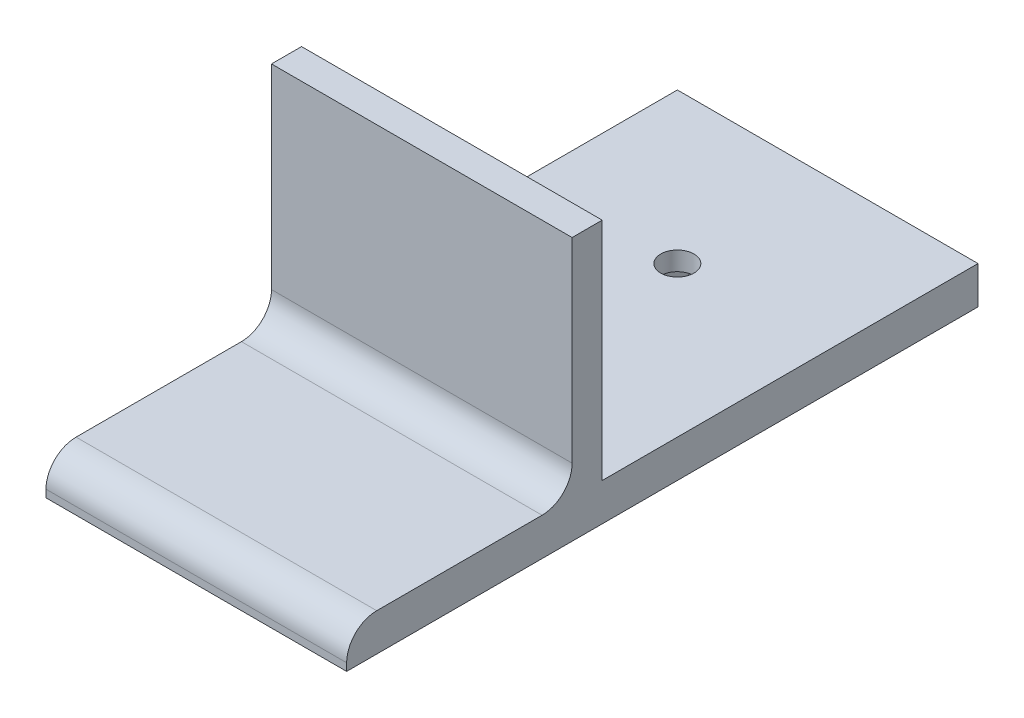
SolidWorks part; units mm, degrees
ref_plane "Front Plane" through (0, 0, 0) normal (0, 0, 1) x (1, 0, 0)
ref_plane "Top Plane" through (0, 0, 0) normal (0, 1, 0) x (1, 0, 0)
ref_plane "Right Plane" through (0, 0, 0) normal (1, 0, 0) x (0, 0, -1)
sketch "Sketch1" plane through (0, 0, 0) normal (1, 0, 0) x (0, 0, -1)
  line L0 (0, 0) -> (106.68, 0)
  line L1 (106.68, 0) -> (106.68, 6.35)
  line L6 (0, 6.35) -> (0, 0)
  line L7 (43.18, 44.45) -> (43.18, 6.35)
  line L8 (43.18, 6.35) -> (106.68, 6.35)
  line L10 (0, 6.35) -> (38.1, 6.35)
  line L11 (38.1, 6.35) -> (38.1, 44.45)
  line L12 (38.1, 44.45) -> (43.18, 44.45)
  dimension "D1" = 5.08
  dimension "D2" = 63.5
  dimension "D3" = 6.35
  dimension "D4" = 38.1
  dimension "D6" = 38.1
extrude "Boss-Extrude1" add sketch "Sketch1" along normal blind 50.8
hole_wizard "#10 Clearance Hole1" positions "Sketch6" profile "Sketch7" hole size "#10" standard "ANSI Inch" end condition through all
sketch "Sketch6" plane through (0, 6.35, 0) normal (0, 1, 0) x (1, 0, 0)
  line L0 (50.8, 43.18) -> (0, 43.18) construction
  line L1 (25.4, 106.68) -> (25.4, 81.28) construction
  line L2 (50.8, 106.68) -> (0, 106.68) construction
  point P0 (25.4, 81.28)
  dimension "D1" = 38.1
sketch "Sketch7" plane through (25.4, 6.35, -81.28) normal (1, 0, 0) x (0, 0, 1)
  line L0 (0, 0) -> (0, 6.35)
  line L1 (0, 6.35) -> (2.8067, 6.35)
  line L2 (2.8067, 6.35) -> (2.8067, 0)
  line L5 (2.8067, 0) -> (0, 0)
  line L11 (0, -6.35) -> (0, 107.95) construction
  dimension "Thru Hole Dia." = 5.6134
  dimension "Thru Hole Depth" = 6.35
sketch "Sketch8" plane through (0, 0, 0) normal (0, -1, 0) x (1, 0, 0)
  line L1 (28.0792, -85.8183) -> (30.6699, -81.2289)
  line L2 (30.6699, -81.2289) -> (27.9907, -76.6906)
  line L3 (27.9907, -76.6906) -> (22.7208, -76.7417)
  line L4 (22.7208, -76.7417) -> (20.1301, -81.3311)
  line L5 (20.1301, -81.3311) -> (22.8093, -85.8694)
  line L6 (22.8093, -85.8694) -> (28.0792, -85.8183)
  circle A0 centre (25.4, -81.28) radius 4.5641 construction
  dimension "D1" = 9.1281
extrude "Cut-Extrude1" cut sketch "Sketch8" against normal blind 3.175
fillet "Fillet1" radius 5.08 2 edges at (25.4, 6.35, 0) (25.4, 6.35, -38.1)
